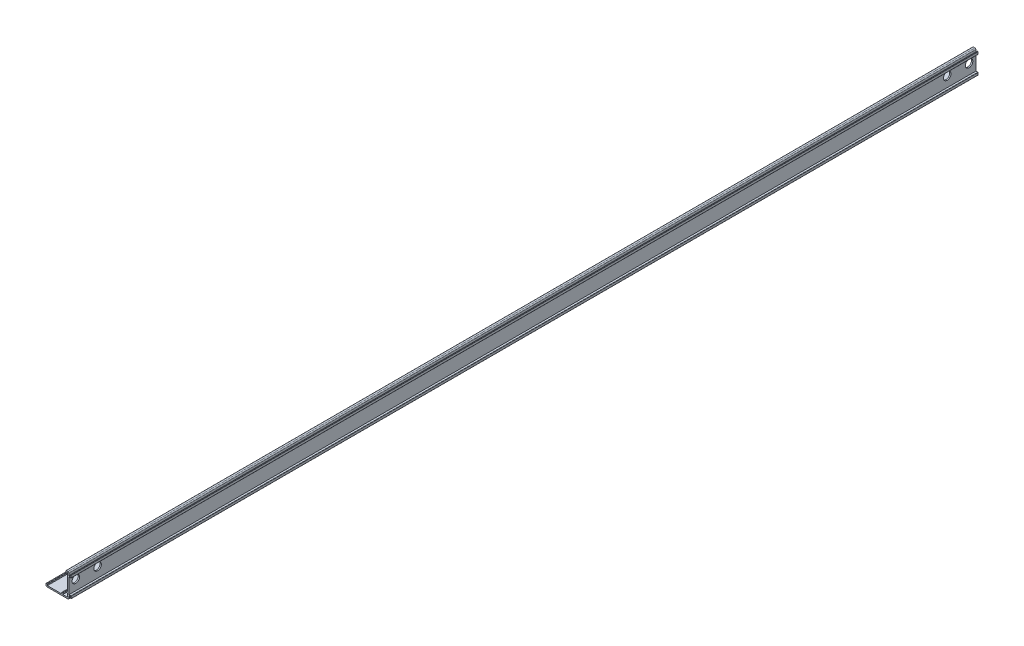
SolidWorks part; units mm, degrees
ref_plane "Front Plane" through (0, 0, 0) normal (0, 0, 1) x (1, 0, 0)
ref_plane "Top Plane" through (0, 0, 0) normal (0, 1, 0) x (1, 0, 0)
ref_plane "Right Plane" through (0, 0, 0) normal (1, 0, 0) x (0, 0, -1)
sketch "Main" plane through (0, 0, 0) normal (0, 1, 0) x (1, 0, 0)
  line L1 (-23.368, -844.55) -> (23.368, -844.55)
  line L2 (-23.368, -844.55) -> (-23.368, 844.55)
  line L3 (-23.368, 844.55) -> (23.368, 844.55)
  line L4 (23.368, -844.55) -> (23.368, 844.55)
  line L5 (-23.368, -844.55) -> (23.368, 844.55) construction
  line L6 (-23.368, 844.55) -> (23.368, -844.55) construction
  point P0 (0, 0)
  dimension "D1" = 1689.1
  dimension "D2" = 46.736
extrude "Extrude-Main" add sketch "Main" along normal blind 44.45
sketch "Main Cut" plane through (0, 0, 844.55) normal (0, 0, 1) x (1, 0, 0)
  line L1 (-23.368, 44.45) -> (13.97, 44.45)
  line L2 (-23.368, 44.45) -> (-23.368, 5.08)
  line L3 (-23.368, 5.08) -> (13.97, 5.08)
  line L4 (13.97, 44.45) -> (13.97, 5.08)
  dimension "D1" = 39.37
  dimension "D2" = 37.338
extrude "Cut-Main" cut sketch "Main Cut" against normal through all
sketch "Bottom Left" plane through (0, 0, 844.55) normal (0, 0, 1) x (1, 0, 0)
  line L0 (-23.368, 5.08) -> (13.97, 5.08) construction
  line L1 (-20.828, 5.08) -> (5.842, 5.08)
  line L2 (-20.828, 5.08) -> (-20.828, 2.413)
  line L3 (-20.828, 2.413) -> (5.842, 2.413)
  line L4 (5.842, 5.08) -> (5.842, 2.413)
  line L5 (-23.368, 5.08) -> (-23.368, 0) construction
  line L6 (-23.368, 0) -> (23.368, 0) construction
  dimension "D1" = 2.54
  dimension "D2" = 26.67
  dimension "D3" = 2.413
extrude "Cut-Bottom Left" cut sketch "Bottom Left" against normal through all
sketch "Bottom Right" plane through (0, 0, 844.55) normal (0, 0, 1) x (1, 0, 0)
  line L0 (5.842, 5.08) -> (13.97, 5.08) construction
  line L1 (7.874, 5.08) -> (13.97, 5.08)
  line L2 (7.874, 5.08) -> (7.874, 2.413)
  line L3 (7.874, 2.413) -> (13.97, 2.413)
  line L4 (13.97, 5.08) -> (13.97, 2.413)
  line L5 (5.842, 2.413) -> (5.842, 5.08) construction
  line L6 (-23.368, 0) -> (23.368, 0) construction
  line L7 (13.97, 5.08) -> (13.97, 44.45) construction
  dimension "D1" = 2.032
  dimension "D2" = 0
  dimension "D3" = 2.413
extrude "Cut-Bottom Right" cut sketch "Bottom Right" against normal through all
sketch "Left Bottom" plane through (0, 0, 844.55) normal (0, 0, 1) x (1, 0, 0)
  line L7 (13.97, 2.413) -> (17.018, 2.413)
  line L8 (13.97, 2.413) -> (13.97, 9.271)
  line L9 (13.97, 9.271) -> (17.018, 9.271)
  line L10 (17.018, 2.413) -> (17.018, 9.271)
  dimension "D1" = 6.858
  dimension "D2" = 3.048
extrude "Cut-Left Bottom" cut sketch "Left Bottom" against normal through all
sketch "Left Middle" plane through (0, 0, 844.55) normal (0, 0, 1) x (1, 0, 0)
  line L0 (13.97, 9.271) -> (13.97, 44.45) construction
  line L1 (13.97, 11.4902) -> (17.018, 11.4902)
  line L2 (13.97, 11.4902) -> (13.97, 41.9702)
  line L3 (13.97, 41.9702) -> (17.018, 41.9702)
  line L4 (17.018, 11.4902) -> (17.018, 41.9702)
  line L5 (17.018, 9.271) -> (17.018, 2.413) construction
  dimension "D1" = 30.48
  dimension "D2" = 0
extrude "Cut-Left Mid" cut sketch "Left Middle" against normal through all
sketch "Right Middle" plane through (0, 0, 844.55) normal (0, 0, 1) x (1, 0, 0)
  line L0 (23.368, 44.45) -> (23.368, 0) construction
  line L1 (19.431, 7.874) -> (27.305, 7.874)
  line L2 (19.431, 7.874) -> (19.431, 36.576)
  line L3 (19.431, 36.576) -> (27.305, 36.576)
  line L4 (27.305, 7.874) -> (27.305, 36.576)
  line L5 (19.431, 7.874) -> (27.305, 36.576) construction
  line L6 (19.431, 36.576) -> (27.305, 7.874) construction
  line L7 (17.018, 11.4902) -> (17.018, 41.9702) construction
  point P0 (23.368, 22.225)
  dimension "D1" = 28.702
  dimension "D2" = 2.413
extrude "Cut-Right Mid" cut sketch "Right Middle" against normal through all
sketch "Hooks" plane through (0, 0, 844.55) normal (0, 0, 1) x (1, 0, 0)
  line L0 (19.431, 22.225) -> (15.4247, 22.225) construction
  line L1 (19.431, 36.576) -> (19.431, 7.874) construction
  line L2 (15.4247, 22.225) -> (33.1764, 22.225) construction
  line L3 (19.431, 44.45) -> (19.431, 38.1635)
  line L4 (13.97, 44.45) -> (23.368, 44.45) construction
  line L5 (19.431, 38.1635) -> (21.7805, 38.1635)
  line L6 (21.7805, 38.1635) -> (21.7805, 41.402)
  line L7 (21.7805, 41.402) -> (23.368, 41.402)
  line L8 (23.368, 44.45) -> (23.368, 36.576) construction
  line L9 (23.368, 41.402) -> (23.368, 44.45)
  line L10 (23.368, 44.45) -> (19.431, 44.45)
  line L11 (23.368, 36.576) -> (19.431, 36.576) construction
  line L12 (23.368, 3.048) -> (23.368, 0)
  line L13 (21.7805, 3.048) -> (23.368, 3.048)
  line L14 (21.7805, 6.2865) -> (21.7805, 3.048)
  line L15 (19.431, 6.2865) -> (21.7805, 6.2865)
  line L16 (19.431, 0) -> (19.431, 6.2865)
  line L17 (23.368, 0) -> (19.431, 0)
  dimension "D1" = 1.5875
  dimension "D2" = 1.5875
  dimension "D3" = 4.826
extrude "Hook Cut" cut sketch "Hooks" against normal through all
fillet "Fillet3" radius 1.905 3 edges at (19.431, 0, 0) (19.431, 44.45, 0) (-23.368, 0, 0)
fillet "Fillet4" radius 0.508 14 edges at (-23.368, 5.08, 0) (-20.828, 5.08, 0) (13.97, 41.9702, 0) (13.97, 44.45, 0) (13.97, 9.271, 0) (13.97, 11.4902, 0) (5.842, 5.08, 0) (7.874, 5.08, 0) (23.368, 41.402, 0) (23.368, 36.576, 0) (23.368, 7.874, 0) (23.368, 3.048, 0) (21.7805, 3.048, 0) (21.7805, 41.402, 0)
sketch "Center Line" plane through (17.018, 0, 0) normal (-1, 0, 0) x (0, 0, 1)
  line L0 (844.55, 26.7302) -> (-844.55, 26.7302) construction
  line L1 (844.55, 11.4902) -> (844.55, 41.9702) construction
  line L2 (-844.55, 11.4902) -> (-844.55, 41.9702) construction
  line L4 (0, 43.942) -> (0, 0) construction
  line L5 (844.55, 43.942) -> (-844.55, 43.942) construction
  point P6 (831.85, 26.7302)
  point P7 (791.21, 26.7302)
  point P16 (-831.85, 26.7302)
  point P18 (-791.21, 26.7302)
  dimension "D1" = 12.7
  dimension "D2" = 53.34
  dimension "D3" = 12.7
  dimension "D4" = 53.34
hole_wizard "Screw Holes" positions "Center Line" profile "Hole" counterbore size "M6" standard "ANSI Metric" end condition through all
sketch "Hole" plane through (17.018, 26.7302, -791.21) normal (0, 1, 0) x (0, 0, 1)
  line L0 (0, 0) -> (0, 6.35)
  line L1 (0, 6.35) -> (3.5, 6.35)
  line L3 (3.5, 6.35) -> (3.5, 4.7)
  line L4 (6.975, 4.7) -> (3.5, 4.7)
  line L5 (6.975, 4.7) -> (6.975, 0.025)
  line L6 (6.975, 0.025) -> (7, 0)
  line L7 (7, 0) -> (0, 0)
  line L8 (-6.975, 0.025) -> (-7, 0) construction
  line L11 (0, -6.35) -> (0, 107.95) construction
  dimension "Thru Hole Dia." = 7
  dimension "Thru Hole Depth" = 6.35
  dimension "C'Bore Dia." = 13.95
  dimension "C'Bore Depth" = 4.7
  dimension "Near C'Sink Dia." = 14
  dimension "Near C'Sink Angle" = 90
